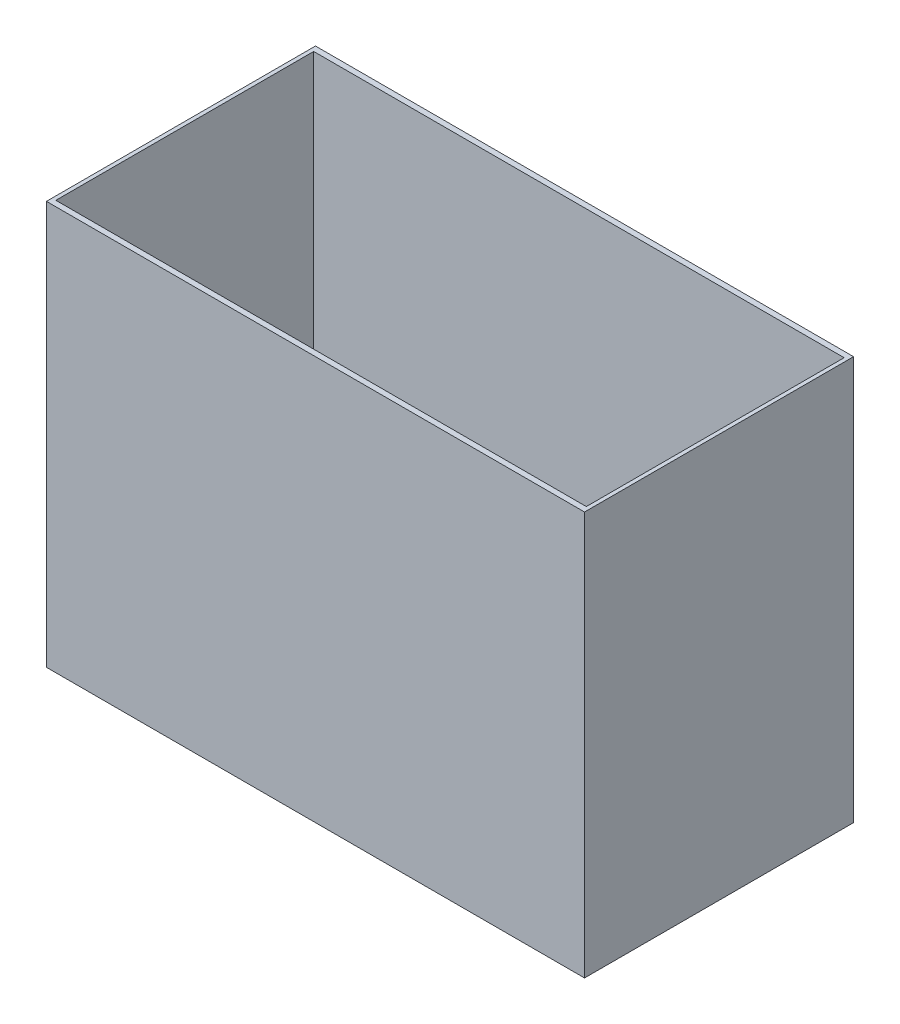
SolidWorks part; units mm, degrees
ref_plane "Front Plane" through (0, 0, 0) normal (0, 0, 1) x (1, 0, 0)
ref_plane "Top Plane" through (0, 0, 0) normal (0, 1, 0) x (1, 0, 0)
ref_plane "Right Plane" through (0, 0, 0) normal (1, 0, 0) x (0, 0, -1)
other "Bounding Box"
ref_plane "Default Plane" through (-292.1, 0, -139.7) normal (0, 1, 0) x (1, 0, 0)
sketch "Sketch1" plane through (0, 0, 0) normal (0, 1, 0) x (1, 0, 0)
  line L0 (-292.1, 0) -> (292.1, 0) construction
  line L1 (-292.1, 139.7) -> (292.1, 139.7)
  line L2 (-292.1, 139.7) -> (-292.1, -139.7)
  line L3 (-292.1, -139.7) -> (292.1, -139.7)
  line L4 (292.1, 139.7) -> (292.1, -139.7)
  line L5 (0, 139.7) -> (0, -139.7) construction
  point P8 (0, 0)
  dimension "D1" = 584.2
  dimension "D2" = 279.4
extrude "Boss-Extrude1" add sketch "Sketch1" along normal blind 12.7
sketch "Sketch2" plane through (0, 12.7, 0) normal (0, 1, 0) x (1, 0, 0)
  line L0 (-245.9259, -63.5) -> (-55.3589, -63.5) construction
  line L1 (-241.3, -120.6497) -> (-152.4, -120.6497)
  line L2 (-241.3, -120.6497) -> (-241.3, -101.5997)
  line L3 (-241.3, -101.5997) -> (-152.4, -101.5997)
  line L4 (-152.4, -120.6497) -> (-152.4, -101.5997)
  line L5 (-241.3, -120.6497) -> (-152.4, -101.5997) construction
  line L6 (-241.3, -101.5997) -> (-152.4, -120.6497) construction
  line L7 (-292.1, 139.7) -> (-292.1, -139.7) construction
  line L8 (-292.1, 0) -> (292.1, 0) construction
  line L9 (292.1, -139.7) -> (292.1, 139.7) construction
  line L10 (0, 0) -> (0, 121.6784) construction
  line L11 (241.3, -101.5997) -> (152.4, -120.6497) construction
  line L12 (241.3, -120.6497) -> (152.4, -101.5997) construction
  line L13 (152.4, -120.6497) -> (152.4, -101.5997)
  line L14 (241.3, -101.5997) -> (152.4, -101.5997)
  line L15 (241.3, -120.6497) -> (241.3, -101.5997)
  line L16 (241.3, -120.6497) -> (152.4, -120.6497)
  point P0 (-196.85, -111.1247)
  point P17 (196.85, -111.1247)
  dimension "D1" = 19.05
  dimension "D2" = 88.9
  dimension "D3" = 38.0997
  dimension "D4" = 50.8
  dimension "D5" = 63.5
extrude "Boss-Extrude2" [suppressed] add sketch "Sketch2" along normal blind 304.8 separate body contours L2 L1 L4 L3
pattern_linear "LPattern1" [suppressed] count 2 spacing 304.8 of bodies 101
pattern_linear "LPattern2" [suppressed] count 2 spacing 215.9 of bodies 101
sketch "Sketch3" plane through (0, 0, 0) normal (0, 1, 0) x (1, 0, 0)
  line L1 (-304.8, -152.4) -> (304.8, -152.4)
  line L2 (-304.8, -152.4) -> (-304.8, 152.4)
  line L3 (-304.8, 152.4) -> (304.8, 152.4)
  line L4 (304.8, -152.4) -> (304.8, 152.4)
  line L5 (-304.8, -152.4) -> (304.8, 152.4) construction
  line L6 (-304.8, 152.4) -> (304.8, -152.4) construction
  line L7 (-300.482, -146.05) -> (300.482, -146.05)
  line L8 (-300.482, -146.05) -> (-300.482, 146.05)
  line L9 (-300.482, 146.05) -> (300.482, 146.05)
  line L10 (300.482, -146.05) -> (300.482, 146.05)
  line L11 (-300.482, -146.05) -> (300.482, 146.05) construction
  line L12 (-300.482, 146.05) -> (300.482, -146.05) construction
  point P0 (0, 0)
  point P6 (0, 0)
  dimension "D1" = 609.6
  dimension "D2" = 304.8
  dimension "D3" = 292.1
  dimension "D4" = 600.964
extrude "Boss-Extrude3" add sketch "Sketch3" along normal blind 457.2 separate body
sketch "Sketch4" plane through (0, 12.7, 0) normal (0, 1, 0) x (1, 0, 0)
  circle A0 centre (273.05, 120.65) radius 2.7781
  circle A1 centre (273.05, 120.65) radius 4 construction
  circle A2 centre (273.05, 120.65) radius 4 construction
  dimension "D1" = 5.5562
extrude "Cut-Extrude1" cut sketch "Sketch4" against normal through all
sketch "Sketch6" plane through (0, 0, 0) normal (0, -1, 0) x (1, 0, 0)
  circle A0 centre (273.05, -120.65) radius 6.35
  circle A1 centre (273.05, -120.65) radius 2.7781 construction
  dimension "D1" = 12.7
extrude "Cut-Extrude2" cut sketch "Sketch6" against normal blind 2.54
mirror "Mirror1" about plane through (0, 0, 0) normal (0, 0, 1) of "Cut-Extrude2", "Cut-Extrude1"
sketch "Sketch7" plane through (0, 12.7, 0) normal (0, 1, 0) x (1, 0, 0)
  line L0 (292.1, 0) -> (49.4912, 0) construction
  line L1 (292.1, -139.7) -> (292.1, 139.7) construction
  circle A0 centre (190.5, 0) radius 4 construction
  circle A1 centre (190.5, 0) radius 2.7781
  dimension "D1" = 8
  dimension "D2" = 5.5562
  dimension "D3" = 101.6
extrude "Cut-Extrude3" cut sketch "Sketch7" against normal through all
sketch "Sketch8" plane through (0, 12.7, 0) normal (0, 1, 0) x (1, 0, 0)
  circle A0 centre (94.9, -12.8415) radius 1.9844 construction
  circle A1 centre (146.1, -12.8415) radius 1.9844 construction
  circle A2 centre (146.1, 12.8415) radius 1.9844 construction
  circle A3 centre (94.9, 12.8415) radius 1.9844 construction
  circle A4 centre (94.9, -12.8415) radius 1.9844
  circle A5 centre (146.1, -12.8415) radius 1.9844
  circle A6 centre (146.1, 12.8415) radius 1.9844
  circle A7 centre (94.9, 12.8415) radius 1.9844
extrude "Cut-Extrude4" cut sketch "Sketch8" against normal through all
sketch "Sketch9" plane through (0, 0, 0) normal (0, -1, 0) x (1, 0, 0)
  circle A1 centre (190.5, 0) radius 6.35
  circle A2 centre (146.1, 12.8415) radius 6.35
  circle A3 centre (94.9, 12.8415) radius 6.35
  circle A4 centre (94.9, -12.8415) radius 6.35
  circle A5 centre (146.1, -12.8415) radius 6.35
  circle A6 centre (273.05, 120.65) radius 6.35 construction
extrude "Cut-Extrude5" cut sketch "Sketch9" against normal blind 3.175
sketch "Sketch11" plane through (0, 0, 0) normal (0, -1, 0) x (1, 0, 0)
  line L0 (-292.1, 139.7) -> (292.1, 139.7) construction
  line L1 (215.9, 139.7) -> (165.1, 139.7)
  line L2 (215.9, 139.7) -> (215.9, 136.525)
  line L3 (215.9, 136.525) -> (165.1, 136.525)
  line L4 (165.1, 139.7) -> (165.1, 136.525)
  line L5 (292.1, 139.7) -> (292.1, -139.7) construction
  dimension "D1" = 3.175
  dimension "D2" = 50.8
  dimension "D3" = 76.2
extrude "Cut-Extrude6" cut sketch "Sketch11" against normal through all
mirror "Mirror2" about plane through (0, 0, 0) normal (0, 0, 1) of "Cut-Extrude6"
